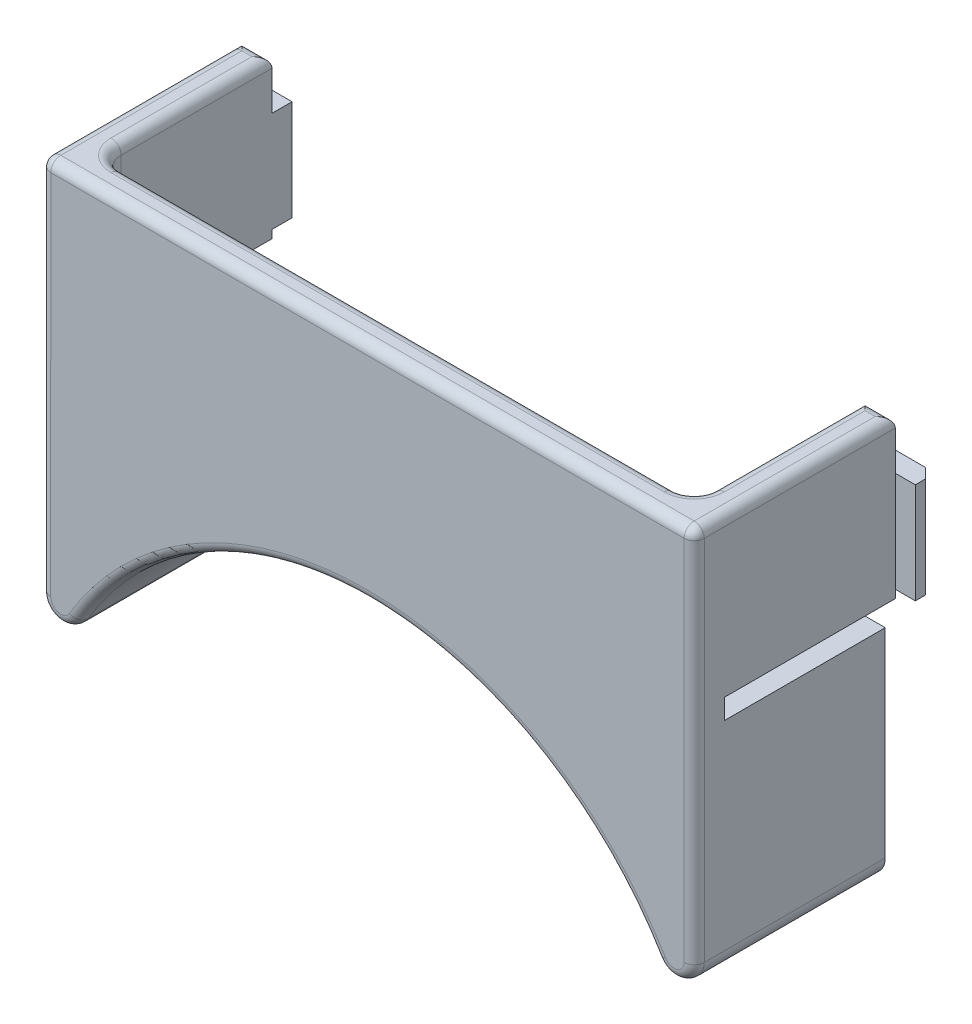
SolidWorks part; units mm, degrees
ref_plane "Front Plane" through (0, 0, 0) normal (0, 0, 1) x (1, 0, 0)
ref_plane "Top Plane" through (0, 0, 0) normal (0, 1, 0) x (1, 0, 0)
ref_plane "Right Plane" through (0, 0, 0) normal (1, 0, 0) x (0, 0, -1)
sketch "Sketch1" plane through (0, 0, 0) normal (0, 0, 1) x (1, 0, 0)
  line L0 (-3.2495, -5.7986) -> (3.25, -5.7986)
  line L1 (3.25, -5.7986) -> (3.25, -10.6554)
  line L2 (3.25, -11.5459) -> (3.25, -7.7128) construction
  line L3 (-3.2495, -5.7986) -> (-3.25, -10.6554)
  line L4 (-3.25, -9.6629) -> (-3.25, -11.5459) construction
  line L5 (-3.2495, -5.8986) -> (3.25, -5.8986)
  circle A0 centre (0, -11.4678) radius 3.35
  circle A1 centre (0, -11.4678) radius 3.125
  circle A2 centre (0, -11.4678) radius 3.125 construction
  dimension "D2" = 6.7
  dimension "D3" = 0.1
  dimension "D1" = 0
extrude "Boss-Extrude1" add sketch "Sketch1" against normal offset from surface (1.9 mm away) 0.1 contours A0 L1 L0 L3
sketch "Sketch2" plane through (0, 0, -1.9) normal (0, 0, -1) x (-1, 0, 0)
  line L0 (-3.25, -5.8986) -> (-3.25, -10.6554) construction
  line L1 (3.2495, -5.8986) -> (-3.25, -5.8986)
  line L2 (3.2495, -5.8986) -> (3.2495, -7.4678)
  line L3 (3.2495, -7.4678) -> (-3.25, -7.4678)
  line L4 (-3.25, -5.8986) -> (-3.25, -7.4678)
  line L5 (-3.5, -7.9678) -> (3.5, -7.9678) construction
  point P9 (-3.25, -5.8986)
  point P10 (-3.25, -7.4678)
  point P11 (3.2495, -7.4678)
  point P12 (3.2495, -5.8986)
  dimension "D1" = 0.5
extrude "Boss-Extrude2" add sketch "Sketch2" along normal up to surface (0.1 mm away)
sketch "Sketch3" plane through (-3.2495, 0, 0) normal (-1, 0, 0) x (0, 0, 1)
  line L0 (-2, -6.3874) -> (-2, -7.3874)
  line L1 (-2, -6.3874) -> (-2.2, -6.3874)
  line L2 (-2, -7.3874) -> (-2.2, -7.3874)
  line L3 (-2.2, -6.3874) -> (-2.2, -7.3874)
  line L4 (-2, -5.8986) -> (-2, -7.4678) construction
  line L5 (-1.2574, -5.3033) -> (-5.0325, -9.0784) construction
  dimension "D1" = 0.2
  dimension "D2" = 1
  dimension "D3" = 0.1
extrude "Boss-Extrude3" add sketch "Sketch3" along normal blind 0.2 and the other way blind 0.3
mirror "Mirror1" about plane through (0, 0, 0) normal (1, 0, 0) of "Boss-Extrude3"
sketch "Sketch4" plane through (0, 0, -2) normal (0, 0, -1) x (-1, 0, 0)
  line L0 (2.9495, -6.3874) -> (2.9495, -5.8986) construction
  line L1 (-3.25, -5.8986) -> (3.2495, -5.8986) construction
  line L2 (-2.9495, -7.3874) -> (-2.9495, -7.9678) construction
  line L3 (-3.5, -7.9678) -> (3.5, -7.9678) construction
  line L5 (-2.9495, -7.9678) -> (2.9495, -7.9678)
  line L6 (-2.9495, -7.9678) -> (-2.9495, -5.8986)
  line L7 (-2.9495, -5.8986) -> (2.9495, -5.8986)
  line L8 (2.9495, -7.9678) -> (2.9495, -5.8986)
extrude "Cut-Extrude1" cut sketch "Sketch4" against normal offset from surface (1.7 mm away) 0.3 up to face at (0.0001, -7.6426, 0)
chamfer "Chamfer1" distance 0.1 angle 45 2 edges at (-3.4495, -6.8874, -2.2) (3.4495, -6.8874, -2.2)
sketch "Sketch5" plane through (0, 0, -1.9) normal (0, 0, -1) x (-1, 0, 0)
  line L0 (2.9495, -7.9678) -> (2.9495, -7.4678) construction
  line L1 (3.2757, -7.4678) -> (2.9495, -7.4678)
  line L2 (3.2757, -7.4678) -> (3.2757, -7.6678)
  line L3 (3.2757, -7.6678) -> (2.9495, -7.6678)
  line L4 (2.9495, -7.4678) -> (2.9495, -7.6678)
  line L5 (0, -5.8986) -> (0, -9.4296) construction
  line L6 (2.9495, -5.8986) -> (-2.9495, -5.8986) construction
  line L7 (0, -11.5459) -> (0, -6.0459) construction
  line L8 (-2.9495, -7.4678) -> (-2.9495, -7.6678)
  line L9 (-3.2757, -7.6678) -> (-2.9495, -7.6678)
  line L10 (-3.2757, -7.4678) -> (-3.2757, -7.6678)
  line L11 (-3.2757, -7.4678) -> (-2.9495, -7.4678)
  line L12 (3.2495, -7.4678) -> (2.9495, -7.4678) construction
  dimension "D1" = 0.2
extrude "Cut-Extrude2" cut sketch "Sketch5" against normal up to surface (1.6 mm away) up to face at (0, -6.9332, -0.3)
fillet "Fillet1" radius 0.2 6 edges at (2.9495, -7.9678, -1.1) (-2.9495, -7.9678, -1.1) (-2.9495, -7.8178, -0.3) (0, -7.9678, -0.3) (2.9495, -7.8178, -0.3) (2.9495, -6.6832, -0.3)
fillet "Fillet2" radius 0.2 2 edges at (-3.25, -10.6554, -0.95) (3.25, -10.6554, -0.95)
fillet "Fillet3" radius 0.1 16 edges at (3.25, -7.7749, 0) (3.1031, -9.844, 0) (0.0001, -8.1178, 0) (-3.103, -9.8439, 0) (-3.2497, -7.7748, 0) (3.25, -5.8986, -1) (0.0002, -5.8986, 0) (-3.2495, -5.8986, -0.95) (-3.2495, -5.8986, -1.95) (-3.0995, -5.8986, -2) (-2.9495, -5.8986, -1.25) (-2.891, -5.8986, -0.3586) (0, -5.8986, -0.3) (2.891, -5.8986, -0.3586) (2.9495, -5.8986, -1.25) (3.0998, -5.8986, -2)
